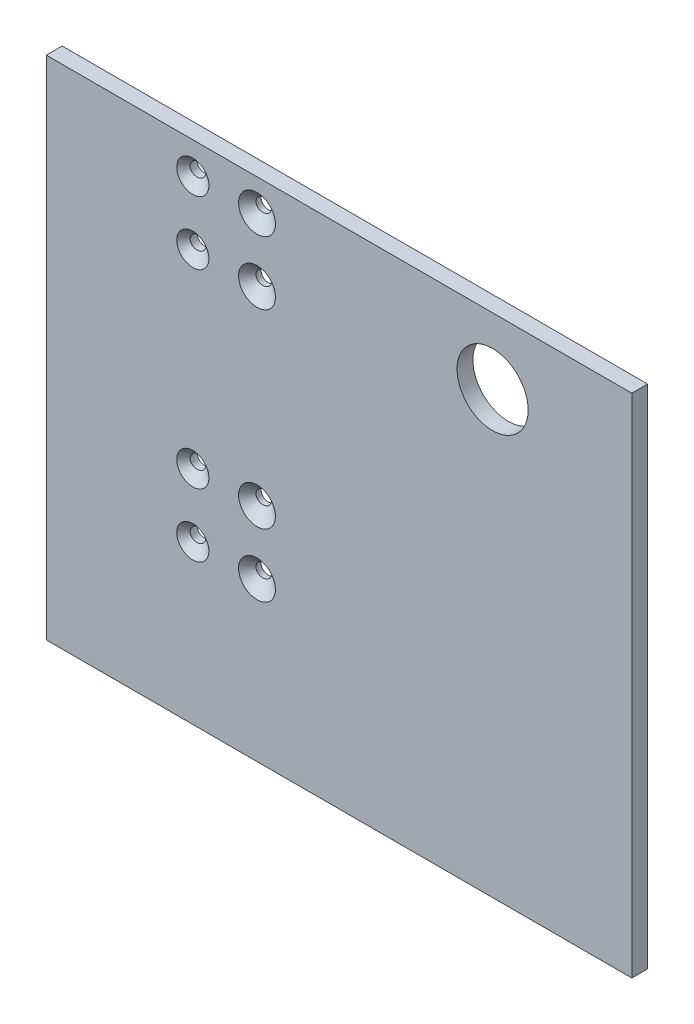
SolidWorks part; units mm, degrees
material "PC High Viscosity"
ref_plane "Front Plane" through (0, 0, 0) normal (0, 0, 1) x (1, 0, 0)
ref_plane "Top Plane" through (0, 0, 0) normal (0, 1, 0) x (1, 0, 0)
ref_plane "Right Plane" through (0, 0, 0) normal (1, 0, 0) x (0, 0, -1)
sketch "Sketch1" plane through (0, 0, 0) normal (0, 0, 1) x (1, 0, 0)
  line L1 (-117.475, -101.6) -> (117.475, -101.6)
  line L2 (-117.475, -101.6) -> (-117.475, 101.6)
  line L3 (-117.475, 101.6) -> (117.475, 101.6)
  line L4 (117.475, -101.6) -> (117.475, 101.6)
  line L5 (-117.475, -101.6) -> (117.475, 101.6) construction
  line L6 (-117.475, 101.6) -> (117.475, -101.6) construction
  point P0 (0, 0)
  dimension "D1" = 234.95
  dimension "D2" = 203.2
extrude "Boss-Extrude1" add sketch "Sketch1" along normal blind 6.35
sketch "Sketch2" plane through (0, 0, 6.35) normal (0, 0, 1) x (1, 0, 0)
  line L0 (117.475, 101.6) -> (-117.475, 101.6) construction
  line L1 (117.475, -101.6) -> (117.475, 101.6) construction
  circle A0 centre (61.595, 74.93) radius 14.2748
  dimension "D3" = 28.5496
  dimension "D1" = 26.67
  dimension "D2" = 55.88
extrude "Cut-Extrude1" cut sketch "Sketch2" against normal through all
hole_wizard "CSK for #10 Flat Head Machine Screw (100)2" positions "Sketch5" profile "Sketch6" countersink size "#10" standard "ANSI Inch" end condition through all
sketch "Sketch5" plane through (271.1777, -265.5951, -36.0344) normal (-0.1349, 0, -0.9909) x (-0.9909, 0, 0.1349)
  point P0 (333.442, 227.4951)
  point P2 (333.442, 252.8951)
  point P4 (333.442, 329.0951)
  point P6 (333.442, 354.4951)
sketch "Sketch6" plane through (-59.217, -38.1, 8.9424) normal (0, 1, 0) x (0.9909, 0, -0.1349)
  line L0 (0, 0) -> (0, 16.7188)
  line L1 (0, 16.7188) -> (2.8067, 16.7188)
  line L2 (2.8067, 16.7188) -> (2.8067, 6.0833)
  line L3 (2.8067, 6.0833) -> (8.89, 0)
  line L4 (8.89, 0) -> (0, 0)
  line L5 (-2.8067, 6.0833) -> (-8.89, 0) construction
  line L6 (0, -6.35) -> (0, 107.95) construction
  dimension "Thru Hole Dia." = 5.6134
  dimension "Thru Hole Depth" = 16.7188
  dimension "Near C'Sink Dia." = 17.78
  dimension "Near C'Sink Angle" = 90
hole_wizard "CSK for #10 Flat Head Machine Screw (100)3" positions "Sketch7" profile "Sketch8" countersink size "#10" standard "ANSI Inch" end condition through all
sketch "Sketch7" plane through (271.5203, -265.5951, -33.5176) normal (-0.1349, 0, -0.9909) x (-0.9909, 0, 0.1349)
  point P0 (308.042, 252.8951)
  point P2 (308.042, 227.4951)
  point P4 (308.042, 329.0951)
  point P6 (308.042, 354.4951)
sketch "Sketch8" plane through (-33.7065, -12.7, 8.033) normal (0, 1, 0) x (0.9909, 0, -0.1349)
  line L0 (0, 0) -> (0, 19.2588)
  line L1 (0, 19.2588) -> (2.8067, 19.2588)
  line L2 (2.8067, 19.2588) -> (2.8067, 6.0833)
  line L3 (2.8067, 6.0833) -> (8.89, 0)
  line L4 (8.89, 0) -> (0, 0)
  line L5 (-2.8067, 6.0833) -> (-8.89, 0) construction
  line L6 (0, -6.35) -> (0, 107.95) construction
  dimension "Thru Hole Dia." = 5.6134
  dimension "Thru Hole Depth" = 19.2588
  dimension "Near C'Sink Dia." = 17.78
  dimension "Near C'Sink Angle" = 90
